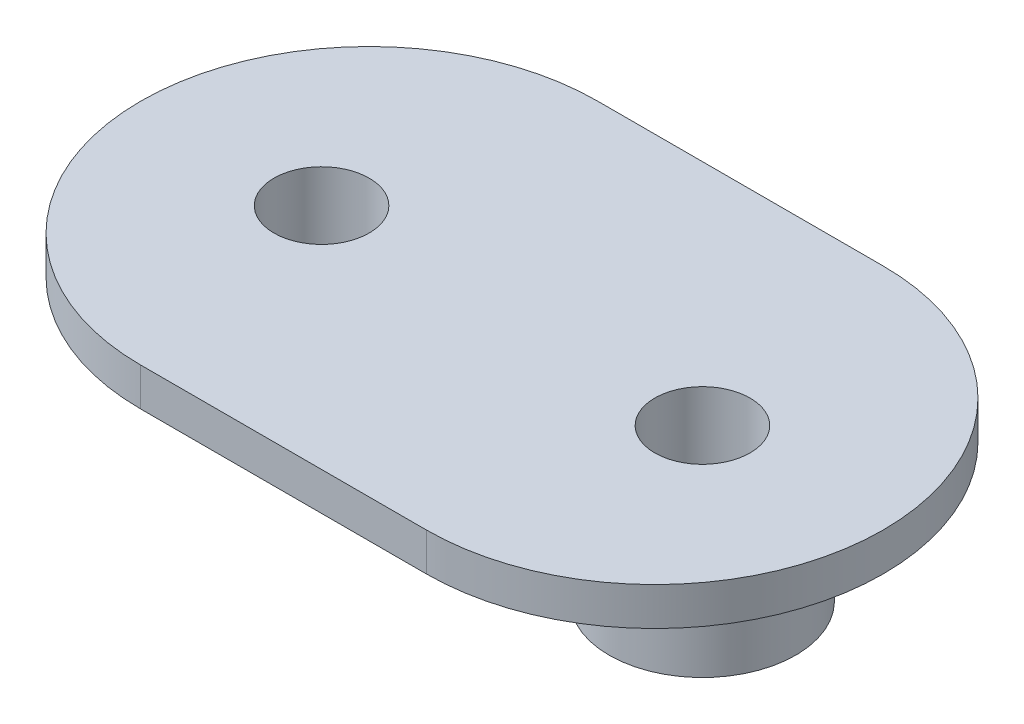
SolidWorks part; units mm, degrees
ref_plane "Front Plane" through (0, 0, 0) normal (0, 0, 1) x (1, 0, 0)
ref_plane "Top Plane" through (0, 0, 0) normal (0, 1, 0) x (1, 0, 0)
ref_plane "Right Plane" through (0, 0, 0) normal (1, 0, 0) x (0, 0, -1)
sketch "Sketch1" plane through (0, 0, 0) normal (0, 1, 0) x (1, 0, 0)
  line L0 (-10, 0) -> (10, 0) construction
  line L3 (-7.5, 12) -> (7.5, 12)
  line L4 (-7.5, -12) -> (7.5, -12)
  circle A2 centre (-10, 0) radius 4.9
  circle A3 centre (10, 0) radius 4.9
  circle A4 centre (-10, 0) radius 2.5
  circle A5 centre (10, 0) radius 2.5
  arc A6 (-7.5, 12) -> (-7.5, -12) centre (-7.5, 0) ccw
  arc A7 (7.5, 12) -> (7.5, -12) centre (7.5, 0) cw
  point P0 (0, 0)
  point P6 (0, 12)
  point P7 (0, -12)
  dimension "D2" = 9.8
  dimension "D3" = 9.8
  dimension "D5" = 5
  dimension "D6" = 5
  dimension "D1" = 20
  dimension "D4" = 15
  dimension "D7" = 10
  dimension "D8" = 15
  dimension "D9" = 10
  dimension "D10" = 24
  dimension "D11" = 12
extrude "Boss-Extrude1" add sketch "Sketch1" along normal blind 2 contours A2 A3 region at (0, 0, 0)
extrude "Boss-Extrude2" add sketch "Sketch1<3>" against normal blind 6 and the other way blind 2 separate body contours A3 A5 | A4 A2 region at (-14.7614, 0, 0) region at (5.2386, 0, 0)
sketch "Sketch1<3>" plane through (0, 0, 0) normal (0, 1, 0) x (1, 0, 0) same geometry as "Sketch1"
sketch "Sketch2" plane through (0, 2, 0) normal (0, 1, 0) x (1, 0, 0)
  circle A0 centre (-10, 0) radius 3.8861
  circle A1 centre (-10, 0) radius 5.7564
  circle A2 centre (10, 0) radius 3.8571
  circle A3 centre (10, 0) radius 6.0784
extrude "Boss-Extrude3" add sketch "Sketch2" against normal blind 2
